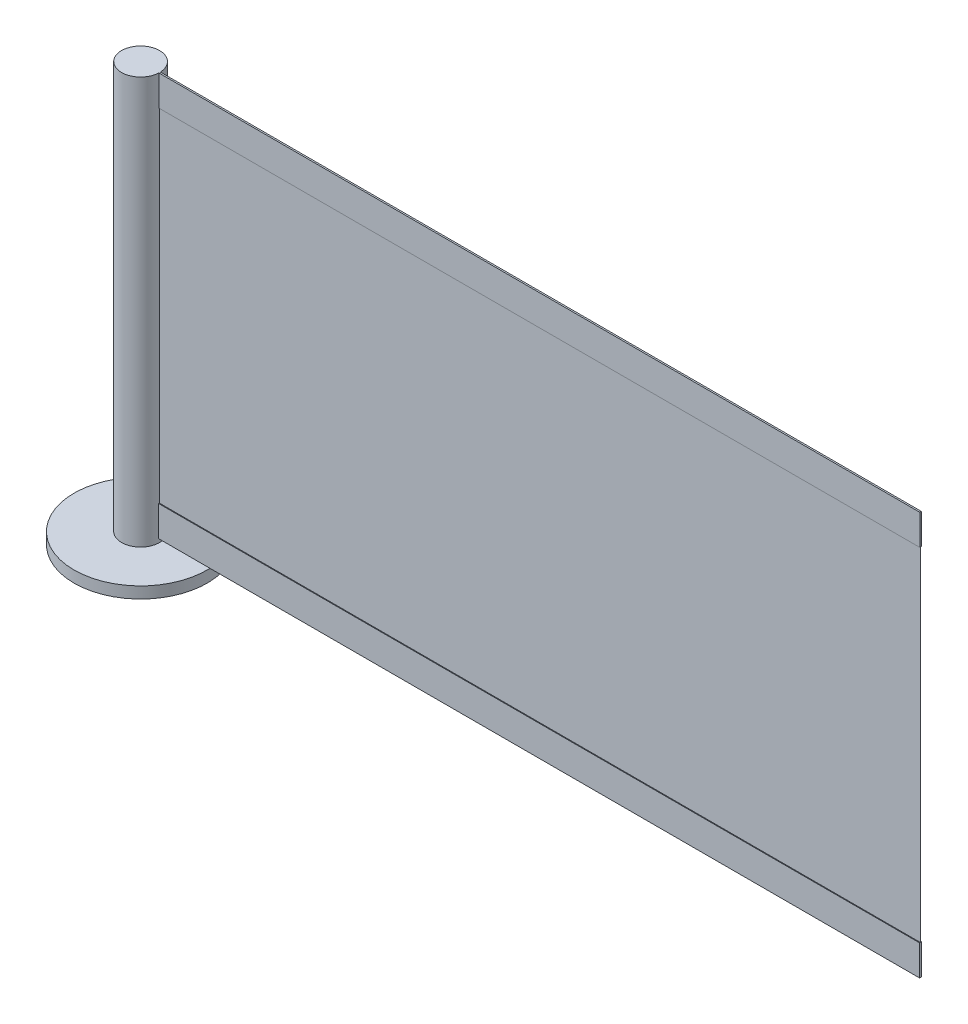
SolidWorks part; units mm, degrees
ref_plane "Front Plane" through (0, 0, 0) normal (0, 0, 1) x (1, 0, 0)
ref_plane "Top Plane" through (0, 0, 0) normal (0, 1, 0) x (1, 0, 0)
ref_plane "Right Plane" through (0, 0, 0) normal (1, 0, 0) x (0, 0, -1)
sketch "Sketch2" plane through (0, 0, 0) normal (0, 1, 0) x (1, 0, 0)
  circle A0 centre (0, 0) radius 175
extrude "Boss-Extrude1" add sketch "Sketch2" along normal blind 30
sketch "Sketch3" plane through (0, 30, 0) normal (0, 1, 0) x (1, 0, 0)
  circle A1 centre (0, 0) radius 50
extrude "Boss-Extrude2" add sketch "Sketch3" along normal blind 1070
sketch "Sketch7" plane through (0, 1100, 0) normal (0, 1, 0) x (1, 0, 0)
  line L0 (0, -0.5) -> (0, 0.5) construction
  line L2 (0, -0.5) -> (2050, -0.5)
  line L3 (0, -0.5) -> (0, 0.5)
  line L4 (0, 0.5) -> (2050, 0.5)
  line L5 (2050, -0.5) -> (2050, 0.5)
  point P5 (0, 0)
  dimension "D1" = 1
  dimension "D2" = 2050
extrude "Boss-Extrude3" add sketch "Sketch7" against normal blind 1060
sketch "Sketch8" plane through (0, 1100, 0) normal (0, 1, 0) x (1, 0, 0)
  line L0 (0, -2) -> (0, 2) construction
  line L2 (0, -2) -> (2050, -2)
  line L3 (0, -2) -> (0, 2)
  line L4 (0, 2) -> (2050, 2)
  line L5 (2050, -2) -> (2050, 2)
  point P4 (0, 0)
  dimension "D1" = 4
  dimension "D2" = 2050
extrude "Boss-Extrude4" add sketch "Sketch8" against normal blind 80
sketch3d "3DSketch2"
  line L0 (2050, 40, 0.5) -> (2050, 40, -0.5) construction
  line L1 (2050, 40, -0.5) -> (49.9975, 40, -0.5) construction
sketch "Sketch11" plane through (0, 40, 0) normal (0, -1, 0) x (-1, 0, 0)
  line L0 (-2050, -2.4692) -> (-2050, 2.4692) construction
  line L2 (-2050, -0.5) -> (-2050, 0.5) construction
  line L4 (-2050, -2.4692) -> (0, -2.4692)
  line L5 (-2050, -2.4692) -> (-2050, 2.4692)
  line L6 (-2050, 2.4692) -> (0, 2.4692)
  line L7 (0, -2.4692) -> (0, 2.4692)
  point P3 (-2050, 0)
  dimension "D1" = 2050
extrude "Boss-Extrude5" add sketch "Sketch11" against normal blind 80
